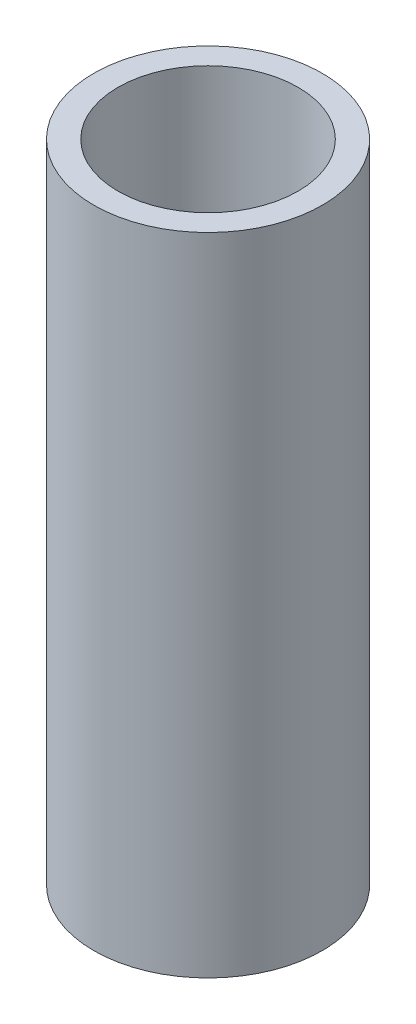
SolidWorks part; units mm, degrees
ref_plane "Front Plane" through (0, 0, 0) normal (0, 0, 1) x (1, 0, 0)
ref_plane "Top Plane" through (0, 0, 0) normal (0, 1, 0) x (1, 0, 0)
ref_plane "Right Plane" through (0, 0, 0) normal (1, 0, 0) x (0, 0, -1)
sketch "Sketch1" plane through (0, 0, 0) normal (0, 1, 0) x (1, 0, 0)
  circle A0 centre (0, 0) radius 17.5
  dimension "SLEEVE_OD" = 35
extrude "Boss-Extrude1" add sketch "Sketch1" along normal blind 98.8739
sketch "Sketch2" plane through (0, 0, 0) normal (0, 1, 0) x (1, 0, 0)
  circle A0 centre (0, 0) radius 13.7888
  dimension "BORE_D" = 27.5777
extrude "Cut-Extrude1" cut sketch "Sketch2" along normal through all
chamfer "Chamfer1" distance 2.0394 angle 58.793 rebuild error yes
